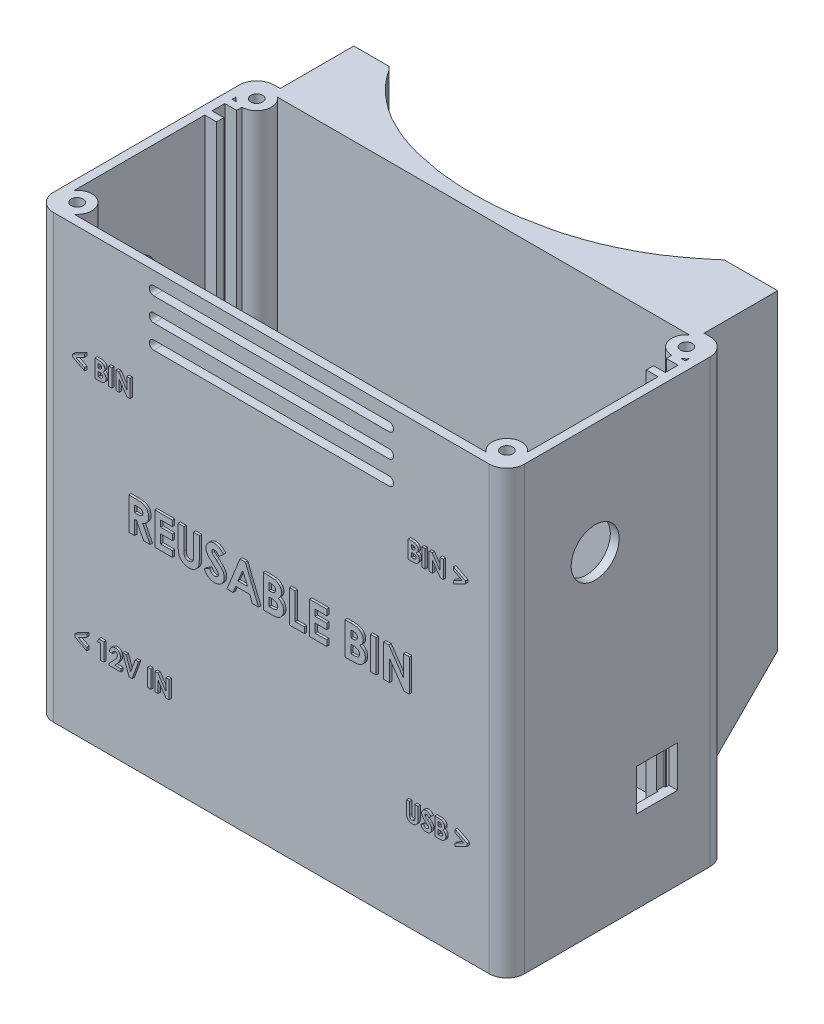
SolidWorks part; units mm, degrees
ref_plane "Front Plane" through (0, 0, 0) normal (0, 0, 1) x (1, 0, 0)
ref_plane "Top Plane" through (0, 0, 0) normal (0, 1, 0) x (1, 0, 0)
ref_plane "Right Plane" through (0, 0, 0) normal (1, 0, 0) x (0, 0, -1)
sketch "Sketch1" plane through (0, 0, 0) normal (0, 1, 0) x (1, 0, 0)
  line L0 (-74, -75) -> (74, -75)
  line L1 (80, -69) -> (80, -6)
  line L2 (74, 0) -> (-74, 0)
  line L3 (-80, -6) -> (-80, -69)
  arc A0 (-80, -69) -> (-74, -75) centre (-74, -69) ccw
  arc A1 (74, -75) -> (80, -69) centre (74, -69) ccw
  arc A2 (80, -6) -> (74, 0) centre (74, -6) ccw
  arc A3 (-74, 0) -> (-80, -6) centre (-74, -6) ccw
extrude "Block" add sketch "Sketch1" along normal blind 150
shell "Shell1" thickness 3 removed face at (0, 150, 37.5)
ref_plane "P1_Top_3" through (0, 3, 0) normal (0, 1, 0) x (1, 0, 0)
sketch "Sketch2" plane through (0, 3, 0) normal (0, 1, 0) x (1, 0, 0)
  circle A0 centre (-73, -7) radius 5
  circle A1 centre (73, -7) radius 5
  circle A2 centre (-73, -68) radius 5
  circle A3 centre (73, -68) radius 5
extrude "Lid columns" add sketch "Sketch2" along normal blind 147
ref_plane "P2_Top_150" through (0, 150, 0) normal (0, 1, 0) x (1, 0, 0)
sketch "Sketch3" plane through (0, 150, 0) normal (0, 1, 0) x (1, 0, 0)
  circle A0 centre (-73, -7) radius 2
  circle A1 centre (73, -7) radius 2
  circle A2 centre (-73, -68) radius 2
  circle A3 centre (73, -68) radius 2
extrude "Lid insert holes" cut sketch "Sketch3" against normal blind 7
ref_plane "P3_Top_3" through (0, 3, 0) normal (0, 1, 0) x (1, 0, 0)
sketch "Sketch4" plane through (0, 3, 0) normal (0, 1, 0) x (1, 0, 0)
  line L1 (-77, -11.35) -> (-73, -11.35)
  line L2 (-77, -11.35) -> (-77, -13.85)
  line L3 (-77, -13.85) -> (-73, -13.85)
  line L4 (-73, -11.35) -> (-73, -13.85)
  line L6 (-77, -18.15) -> (-73, -18.15)
  line L7 (-77, -18.15) -> (-77, -20.65)
  line L8 (-77, -20.65) -> (-73, -20.65)
  line L9 (-73, -18.15) -> (-73, -20.65)
  line L11 (77, -11.35) -> (73, -11.35)
  line L12 (77, -11.35) -> (77, -13.85)
  line L13 (77, -13.85) -> (73, -13.85)
  line L14 (73, -11.35) -> (73, -13.85)
  line L16 (77, -18.15) -> (73, -18.15)
  line L17 (77, -18.15) -> (77, -20.65)
  line L18 (77, -20.65) -> (73, -20.65)
  line L19 (73, -18.15) -> (73, -20.65)
extrude "Plate groove ribs" add sketch "Sketch4" along normal blind 147
ref_plane "P4_Top_19" through (0, 19, 0) normal (0, 1, 0) x (1, 0, 0)
sketch "Sketch5" plane through (0, 19, 0) normal (0, 1, 0) x (1, 0, 0)
  line L0 (-72, -1.5) -> (-72, 25)
  line L1 (-72, 25) -> (-71, 25)
  line L2 (-71, 25) -> (-70, 25)
  line L3 (-70, 25) -> (-69, 25)
  line L4 (-69, 25) -> (-68, 25)
  line L5 (-68, 25) -> (-67, 25)
  line L6 (-67, 25) -> (-66, 25)
  line L7 (-66, 25) -> (-65, 25)
  line L8 (-65, 25) -> (-64, 25)
  line L9 (-64, 25) -> (-63, 25)
  line L10 (-63, 25) -> (-62, 25)
  line L11 (-62, 25) -> (-61, 25)
  line L12 (-61, 25) -> (-60, 25)
  line L13 (-60, 25) -> (-59, 24)
  line L14 (-59, 24) -> (-58, 22.5)
  line L15 (-58, 22.5) -> (-57, 21.2)
  line L16 (-57, 21.2) -> (-56, 19.9)
  line L17 (-56, 19.9) -> (-55, 18.8)
  line L18 (-55, 18.8) -> (-54, 17.7)
  line L19 (-54, 17.7) -> (-53, 16.8)
  line L20 (-53, 16.8) -> (-52, 15.8)
  line L21 (-52, 15.8) -> (-51, 15)
  line L22 (-51, 15) -> (-50, 14.1)
  line L23 (-50, 14.1) -> (-49, 13.4)
  line L24 (-49, 13.4) -> (-48, 12.6)
  line L25 (-48, 12.6) -> (-47, 11.9)
  line L26 (-47, 11.9) -> (-46, 11.3)
  line L27 (-46, 11.3) -> (-45, 10.6)
  line L28 (-45, 10.6) -> (-44, 10)
  line L29 (-44, 10) -> (-43, 9.5)
  line L30 (-43, 9.5) -> (-42, 9)
  line L31 (-42, 9) -> (-41, 8.5)
  line L32 (-41, 8.5) -> (-40, 8)
  line L33 (-40, 8) -> (-39, 7.5)
  line L34 (-39, 7.5) -> (-38, 7.1)
  line L35 (-38, 7.1) -> (-37, 6.7)
  line L36 (-37, 6.7) -> (-36, 6.3)
  line L37 (-36, 6.3) -> (-35, 6)
  line L38 (-35, 6) -> (-34, 5.6)
  line L39 (-34, 5.6) -> (-33, 5.3)
  line L40 (-33, 5.3) -> (-32, 5)
  line L41 (-32, 5) -> (-31, 4.7)
  line L42 (-31, 4.7) -> (-30, 4.4)
  line L43 (-30, 4.4) -> (-29, 4.2)
  line L44 (-29, 4.2) -> (-28, 4)
  line L45 (-28, 4) -> (-27, 3.8)
  line L46 (-27, 3.8) -> (-26, 3.6)
  line L47 (-26, 3.6) -> (-25, 3.4)
  line L48 (-25, 3.4) -> (-24, 3.2)
  line L49 (-24, 3.2) -> (-23, 3)
  line L50 (-23, 3) -> (-22, 2.8)
  line L51 (-22, 2.8) -> (-21, 2.6)
  line L52 (-21, 2.6) -> (-20, 2.5)
  line L53 (-20, 2.5) -> (-19, 2.4)
  line L54 (-19, 2.4) -> (-18, 2.2)
  line L55 (-18, 2.2) -> (-17, 2.2)
  line L56 (-17, 2.2) -> (-16, 2.1)
  line L57 (-16, 2.1) -> (-15, 2)
  line L58 (-15, 2) -> (-14, 1.9)
  line L59 (-14, 1.9) -> (-13, 1.9)
  line L60 (-13, 1.9) -> (-12, 1.8)
  line L61 (-12, 1.8) -> (-11, 1.8)
  line L62 (-11, 1.8) -> (-10, 1.8)
  line L63 (-10, 1.8) -> (-9, 1.8)
  line L64 (-9, 1.8) -> (-8, 1.7)
  line L65 (-8, 1.7) -> (-7, 1.8)
  line L66 (-7, 1.8) -> (-6, 1.8)
  line L67 (-6, 1.8) -> (-5, 1.8)
  line L68 (-5, 1.8) -> (-4, 1.8)
  line L69 (-4, 1.8) -> (-3, 1.9)
  line L70 (-3, 1.9) -> (-2, 2)
  line L71 (-2, 2) -> (-1, 2)
  line L72 (-1, 2) -> (0, 2.1)
  line L73 (0, 2.1) -> (1, 2.2)
  line L74 (1, 2.2) -> (2, 2.3)
  line L75 (2, 2.3) -> (3, 2.4)
  line L76 (3, 2.4) -> (4, 2.5)
  line L77 (4, 2.5) -> (5, 2.6)
  line L78 (5, 2.6) -> (6, 2.8)
  line L79 (6, 2.8) -> (7, 2.9)
  line L80 (7, 2.9) -> (8, 3.1)
  line L81 (8, 3.1) -> (9, 3.3)
  line L82 (9, 3.3) -> (10, 3.5)
  line L83 (10, 3.5) -> (11, 3.7)
  line L84 (11, 3.7) -> (12, 3.9)
  line L85 (12, 3.9) -> (13, 4.1)
  line L86 (13, 4.1) -> (14, 4.3)
  line L87 (14, 4.3) -> (15, 4.5)
  line L88 (15, 4.5) -> (16, 4.7)
  line L89 (16, 4.7) -> (17, 5)
  line L90 (17, 5) -> (18, 5.2)
  line L91 (18, 5.2) -> (19, 5.5)
  line L92 (19, 5.5) -> (20, 5.9)
  line L93 (20, 5.9) -> (21, 6.1)
  line L94 (21, 6.1) -> (22, 6.5)
  line L95 (22, 6.5) -> (23, 6.8)
  line L96 (23, 6.8) -> (24, 7.1)
  line L97 (24, 7.1) -> (25, 7.5)
  line L98 (25, 7.5) -> (26, 7.9)
  line L99 (26, 7.9) -> (27, 8.2)
  line L100 (27, 8.2) -> (28, 8.6)
  line L101 (28, 8.6) -> (29, 9.1)
  line L102 (29, 9.1) -> (30, 9.5)
  line L103 (30, 9.5) -> (31, 9.9)
  line L104 (31, 9.9) -> (32, 10.4)
  line L105 (32, 10.4) -> (33, 10.9)
  line L106 (33, 10.9) -> (34, 11.4)
  line L107 (34, 11.4) -> (35, 11.9)
  line L108 (35, 11.9) -> (36, 12.4)
  line L109 (36, 12.4) -> (37, 12.9)
  line L110 (37, 12.9) -> (38, 13.5)
  line L111 (38, 13.5) -> (39, 14.1)
  line L112 (39, 14.1) -> (40, 14.7)
  line L113 (40, 14.7) -> (41, 15.3)
  line L114 (41, 15.3) -> (42, 15.9)
  line L115 (42, 15.9) -> (43, 16.7)
  line L116 (43, 16.7) -> (44, 17.3)
  line L117 (44, 17.3) -> (45, 18)
  line L118 (45, 18) -> (46, 18.7)
  line L119 (46, 18.7) -> (47, 19.5)
  line L120 (47, 19.5) -> (48, 20.2)
  line L121 (48, 20.2) -> (49, 21)
  line L122 (49, 21) -> (50, 21.8)
  line L123 (50, 21.8) -> (51, 22.6)
  line L124 (51, 22.6) -> (52, 23.4)
  line L125 (52, 23.4) -> (53, 24.3)
  line L126 (53, 24.3) -> (54, 25)
  line L127 (54, 25) -> (55, 25)
  line L128 (55, 25) -> (56, 25)
  line L129 (56, 25) -> (57, 25)
  line L130 (57, 25) -> (58, 25)
  line L131 (58, 25) -> (59, 25)
  line L132 (59, 25) -> (60, 25)
  line L133 (60, 25) -> (61, 25)
  line L134 (61, 25) -> (62, 25)
  line L135 (62, 25) -> (63, 25)
  line L136 (63, 25) -> (64, 25)
  line L137 (64, 25) -> (65, 25)
  line L138 (65, 25) -> (66, 25)
  line L139 (66, 25) -> (67, 25)
  line L140 (67, 25) -> (68, 25)
  line L141 (68, 25) -> (69, 25)
  line L142 (69, 25) -> (70, 25)
  line L143 (70, 25) -> (71, 25)
  line L144 (71, 25) -> (72, 25)
  line L145 (72, 25) -> (72, -1.5)
  line L146 (72, -1.5) -> (-72, -1.5)
extrude "Curved face to the bin" add sketch "Sketch5" along normal blind 131
ref_plane "P5_Right_-81" through (-81, 0, 0) normal (1, 0, 0) x (0, 0, -1)
sketch "Sketch6" plane through (-81, 0, 0) normal (1, 0, 0) x (0, 0, -1)
  line L0 (0, 19) -> (26, 19)
  line L1 (26, 19) -> (26, 45)
  line L2 (26, 45) -> (0, 19)
extrude "Curved face 45-degree underside" cut sketch "Sketch6" along normal blind 162
ref_plane "P6_Right_-80" through (-80, 0, 0) normal (1, 0, 0) x (0, 0, -1)
sketch "Sketch7" plane through (-80, 0, 0) normal (1, 0, 0) x (0, 0, -1)
  circle A0 centre (-45, 30) radius 8.15
  circle A1 centre (-45, 112) radius 8.15
extrude "Back-end holes (12 V, bin A)" cut sketch "Sketch7" along normal blind 3.5
ref_plane "P7_Right_80" through (80, 0, 0) normal (1, 0, 0) x (0, 0, -1)
sketch "Sketch8" plane through (80, 0, 0) normal (1, 0, 0) x (0, 0, -1)
  line L1 (-31, 28) -> (-17, 28)
  line L2 (-31, 28) -> (-31, 42)
  line L3 (-31, 42) -> (-17, 42)
  line L4 (-17, 28) -> (-17, 42)
  line L5 (-31, 28) -> (-17, 42) construction
  line L6 (-31, 42) -> (-17, 28) construction
  circle A0 centre (-45, 112) radius 8.15
  point P2 (-24, 35)
extrude "Front-end holes (bin B, USB)" cut sketch "Sketch8" against normal blind 3.5
ref_plane "P8_Front_75" through (0, 0, 75) normal (0, 0, 1) x (1, 0, 0)
sketch "Sketch9" plane through (0, 0, 75) normal (0, 0, 1) x (1, 0, 0)
  line L0 (-40, 128) -> (40, 128) construction
  line L1 (-40, 129.5) -> (40, 129.5)
  line L2 (-40, 126.5) -> (40, 126.5)
  line L3 (-40, 136) -> (40, 136) construction
  line L4 (-40, 137.5) -> (40, 137.5)
  line L5 (-40, 134.5) -> (40, 134.5)
  line L6 (-40, 144) -> (40, 144) construction
  line L7 (-40, 145.5) -> (40, 145.5)
  line L8 (-40, 142.5) -> (40, 142.5)
  arc A0 (-40, 129.5) -> (-40, 126.5) centre (-40, 128) ccw
  arc A1 (40, 126.5) -> (40, 129.5) centre (40, 128) ccw
  arc A2 (-40, 137.5) -> (-40, 134.5) centre (-40, 136) ccw
  arc A3 (40, 134.5) -> (40, 137.5) centre (40, 136) ccw
  arc A4 (-40, 145.5) -> (-40, 142.5) centre (-40, 144) ccw
  arc A5 (40, 142.5) -> (40, 145.5) centre (40, 144) ccw
  point P2 (0, 128)
  point P7 (0, 136)
  point P14 (0, 144)
  point P21 (0, 0)
extrude "Vents" cut sketch "Sketch9" against normal blind 4
sketch "Sketch10" plane through (0, 0, 75) normal (0, 0, 1) x (1, 0, 0)
  text T0 "REUSABLE BIN" font "Century Gothic" height 11
  text T1 "< 12V IN" font "Century Gothic" height 6
  text T2 "< BIN" font "Century Gothic" height 6
  text T3 "BIN >" font "Century Gothic" height 6
  text T4 "USB >" font "Century Gothic" height 6
extrude "Outer text (raised)" add sketch "Sketch10" along normal blind 0.8
ref_plane "P9_Top_3" through (0, 3, 0) normal (0, 1, 0) x (1, 0, 0)
sketch "Sketch11" plane through (0, 3, 0) normal (0, 1, 0) x (1, 0, 0)
  line L1 (-63.3, -3) -> (-36.7, -3)
  line L2 (-63.3, -3) -> (-63.3, -20.3)
  line L3 (-63.3, -20.3) -> (-36.7, -20.3)
  line L4 (-36.7, -3) -> (-36.7, -20.3)
  line L6 (36.7, -3) -> (63.3, -3)
  line L7 (36.7, -3) -> (36.7, -20.3)
  line L8 (36.7, -20.3) -> (63.3, -20.3)
  line L9 (63.3, -3) -> (63.3, -20.3)
extrude "Tongue pads" add sketch "Sketch11" along normal blind 5
sketch "Sketch12" plane through (0, 0, 0) normal (0, 1, 0) x (1, 0, 0)
  line L1 (-60.3, 1) -> (-39.7, 1)
  line L2 (-60.3, 1) -> (-60.3, -17.3)
  line L3 (-60.3, -17.3) -> (-39.7, -17.3)
  line L4 (-39.7, 1) -> (-39.7, -17.3)
  line L6 (39.7, 1) -> (60.3, 1)
  line L7 (39.7, 1) -> (39.7, -17.3)
  line L8 (39.7, -17.3) -> (60.3, -17.3)
  line L9 (60.3, 1) -> (60.3, -17.3)
extrude "Tongue pockets" cut sketch "Sketch12" along normal blind 3.3
sketch "Sketch13" plane through (0, 0, 0) normal (0, 1, 0) x (1, 0, 0)
  circle A0 centre (-50, -7) radius 2.65
  circle A1 centre (50, -7) radius 2.65
extrude "Peg holes (blind)" cut sketch "Sketch13" along normal blind 6.4
